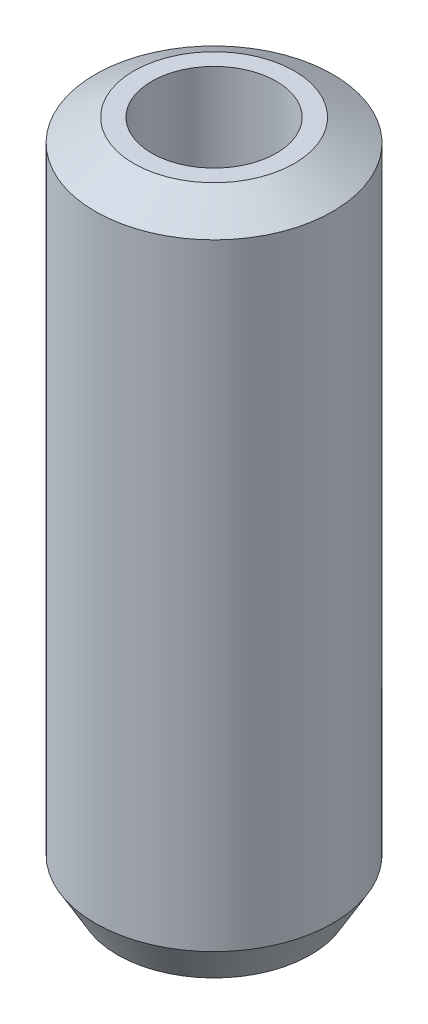
SolidWorks part; units mm, degrees
ref_plane "Front Plane" through (0, 0, 0) normal (0, 0, 1) x (1, 0, 0)
ref_plane "Top Plane" through (0, 0, 0) normal (0, 1, 0) x (1, 0, 0)
ref_plane "Right Plane" through (0, 0, 0) normal (1, 0, 0) x (0, 0, -1)
sketch "Sketch1" plane through (0, 0, 0) normal (0, 1, 0) x (1, 0, 0)
  circle A0 centre (0, 0) radius 5
  dimension "SHAFT_OD" = 10
extrude "Boss-Extrude1" add sketch "Sketch1" along normal blind 28.5071
sketch "Sketch2" plane through (0, 0, 0) normal (0, 1, 0) x (1, 0, 0)
  circle A0 centre (0, 0) radius 2.6237
  dimension "BORE_D" = 5.2474
extrude "Cut-Extrude1" cut sketch "Sketch2" along normal through all
chamfer "Chamfer1" distance 0.9361 angle 60 2 edges at (0, 28.5071, 5) (0, 0, 5) first distance on face at (0, 28.5071, 5) first distance on face at (0, 0, 2.6237)
